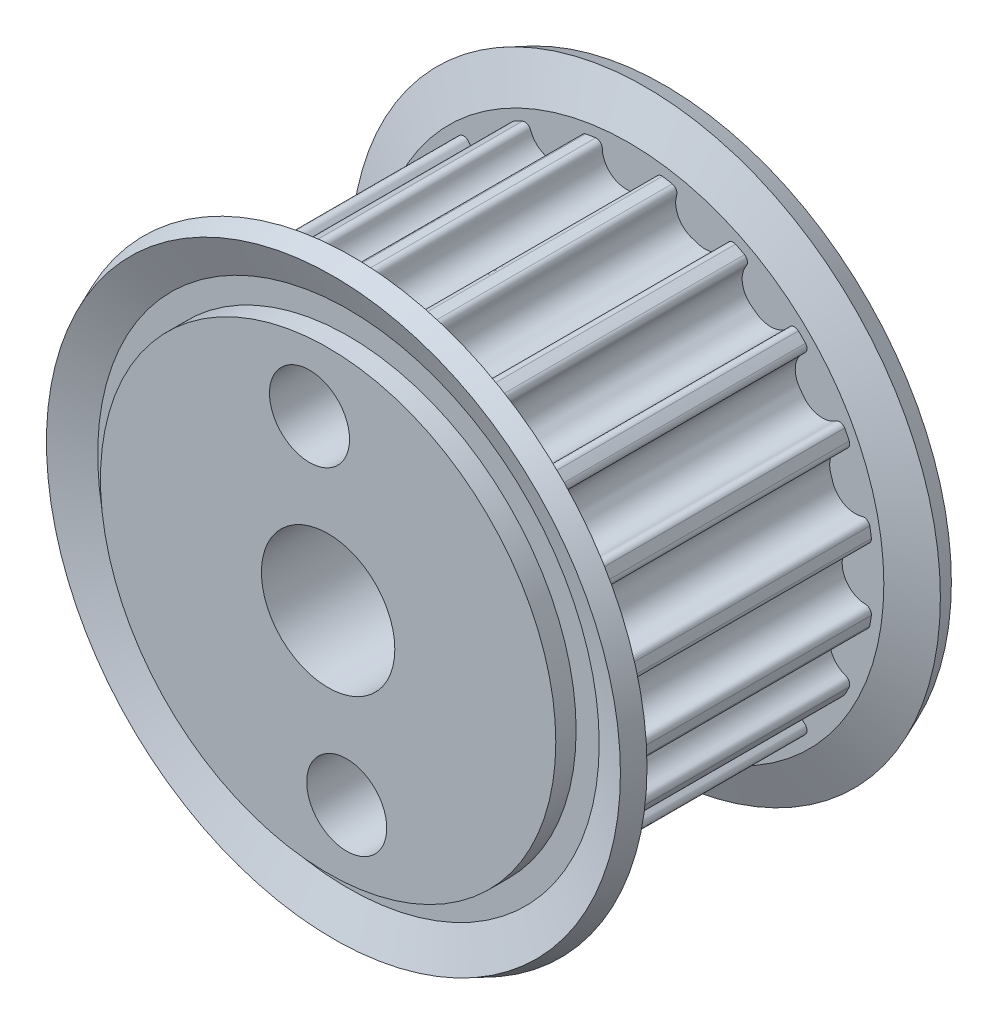
SolidWorks part; units mm, degrees
ref_plane "前视基准面" through (0, 0, 0) normal (0, 0, 1) x (1, 0, 0)
ref_plane "上视基准面" through (0, 0, 0) normal (0, 1, 0) x (1, 0, 0)
ref_plane "右视基准面" through (0, 0, 0) normal (1, 0, 0) x (0, 0, -1)
ref_axis "基准轴1" through (0, 0, 55) along (0, 0, -1)
sketch "SketchRevolveGearBelt01" plane through (0, 0, 0) normal (1, 0, 0) x (0, 0, -1)
  line L0 (0, 0) -> (1, 0) construction
  line L1 (6.4008, 0) -> (6.4008, 8.5326)
  line L2 (6.4008, 8.5326) -> (5.6388, 8.5326)
  line L3 (5.6388, 8.5326) -> (5.6388, 9.397)
  line L4 (5.6388, 9.397) -> (6.2015, 10.7556)
  line L5 (6.2015, 10.7556) -> (5.4975, 11.0472)
  line L6 (5.4975, 11.0472) -> (4.8768, 9.5486)
  line L7 (4.8768, 9.5486) -> (4.8768, 9.1676)
  line L8 (4.8768, 9.1676) -> (-4.8768, 9.1676)
  line L9 (-4.8768, 9.1676) -> (-4.8768, 9.5486)
  line L10 (-4.8768, 9.5486) -> (-5.4975, 11.0472)
  line L11 (-5.4975, 11.0472) -> (-6.2015, 10.7556)
  line L12 (-6.2015, 10.7556) -> (-5.6388, 9.397)
  line L13 (-5.6388, 9.397) -> (-5.6388, 8.5326)
  line L14 (-5.6388, 8.5326) -> (-6.4008, 8.5326)
  line L15 (-6.4008, 8.5326) -> (-6.4008, 0)
  line L16 (-6.4008, 0) -> (6.4008, 0)
  dimension "GearBeltFlange1OutsideLength" = 0.8644
  dimension "GearBeltFlange1X" = 0.5627
  dimension "GearBeltFlange1Y" = 1.3586
  dimension "GearBeltFlangeThickness" = 0.762
  dimension "GearBeltFlangeInside" = 0.381
  dimension "GearBeltOutsideDiameter" = 9.1676
  dimension "GearBeltFlange2X" = 0.5627
revolve "GearBelt01" add sketch "SketchRevolveGearBelt01" angle 360 about L0
sketch "SketchToothGearBelt01" plane through (0, 0, 0) normal (0, 0, 1) x (1, 0, 0)
  arc A0 (9.0809, 1.2614) -> (9.0809, -1.2614) centre (0, 0) cw
  spline S0 degree 3 poles (9.0809, -1.2614) (9.0827, -1.2485) (9.0837, -1.229) (9.0817, -1.203) (9.0786, -1.1837) (9.0738, -1.1647) (9.0675, -1.1462) (9.0596, -1.1283) (9.0502, -1.1112) (9.0393, -1.0949) (9.0272, -1.0796) (9.0137, -1.0654) (8.9991, -1.0524) (8.9835, -1.0407) (8.9669, -1.0303) (8.9495, -1.0215) (8.9314, -1.0141) (8.9127, -1.0083) (8.8936, -1.004) (8.8349, -0.9971) (8.7588, -0.996) (8.6681, -0.9767) (8.601, -0.9578) (8.5356, -0.9335) (8.4723, -0.9041) (8.4115, -0.8699) (8.3536, -0.8311) (8.2989, -0.7878) (8.2477, -0.7404) (8.2005, -0.6891) (8.1573, -0.6343) (8.1186, -0.5762) (8.0846, -0.5154) (8.0555, -0.452) (8.0314, -0.3865) (8.0124, -0.3194) (7.9989, -0.251) (7.9906, -0.1817) (7.9885, -0.1166) (7.989, -0.056) (7.9888, 0) (7.989, 0.056) (7.9885, 0.1166) (7.9906, 0.1817) (7.9989, 0.251) (8.0124, 0.3194) (8.0314, 0.3865) (8.0555, 0.452) (8.0846, 0.5154) (8.1186, 0.5762) (8.1573, 0.6343) (8.2005, 0.6891) (8.2477, 0.7404) (8.2989, 0.7878) (8.3536, 0.8311) (8.4115, 0.8699) (8.4723, 0.9041) (8.5356, 0.9335) (8.601, 0.9578) (8.6681, 0.9767) (8.7588, 0.996) (8.8349, 0.9971) (8.8936, 1.004) (8.9127, 1.0083) (8.9314, 1.0141) (8.9495, 1.0215) (8.9669, 1.0303) (8.9835, 1.0407) (8.9991, 1.0524) (9.0137, 1.0654) (9.0272, 1.0796) (9.0393, 1.0949) (9.0502, 1.1112) (9.0596, 1.1283) (9.0675, 1.1462) (9.0738, 1.1647) (9.0786, 1.1837) (9.0817, 1.203) (9.0837, 1.229) (9.0827, 1.2485) (9.0809, 1.2614) knots 0 0 0 0 0.010413 0.01562 0.020826 0.026033 0.031239 0.036446 0.041652 0.046859 0.052065 0.057272 0.062478 0.067685 0.072891 0.078098 0.083304 0.088511 0.093717 0.098924 0.135739 0.154317 0.172895 0.191472 0.21005 0.228628 0.247206 0.265784 0.284362 0.302939 0.321517 0.340095 0.358673 0.377251 0.395829 0.414406 0.432984 0.451562 0.47014 0.48507 0.5 0.51493 0.52986 0.548438 0.567016 0.585594 0.604171 0.622749 0.641327 0.659905 0.678483 0.697061 0.715638 0.734216 0.752794 0.771372 0.78995 0.808528 0.827105 0.845683 0.864261 0.901076 0.906283 0.911489 0.916696 0.921902 0.927109 0.932315 0.937522 0.942728 0.947935 0.953141 0.958348 0.963554 0.968761 0.973967 0.979174 0.98438 0.989587 1 1 1 1
extrude "ToothExtrudeCutGearBelt01" cut sketch "SketchToothGearBelt01" against normal blind 4.8768 and the other way blind 4.8768
pattern_circular "PatternGearBelt01" count 20 every 18 about axis through (0, 0, 55) along (0, 0, -1) of "ToothExtrudeCutGearBelt01"
sketch "BoreRevolveSketch" plane through (0, 0, 0) normal (1, 0, 0) x (0, 0, -1)
  line L0 (0, 0) -> (1, 0) construction
  line L1 (-6.4008, 0) -> (6.4008, 0)
  line L2 (6.4008, 0) -> (6.4008, 2.5)
  line L3 (6.4008, 2.5) -> (-6.4008, 2.5)
  line L4 (-6.4008, 2.5) -> (-6.4008, 0)
  dimension "TaperSide1" = 2.5
  dimension "TaperSide2" = 2.5
revolve "BoreRevolveCut" cut sketch "BoreRevolveSketch" angle 360 about L0
sketch "AuxiliarySketchGearBelt01" plane through (0, 0, 0) normal (0, 0, 1) x (1, 0, 0)
  circle A0 centre (0, 0) radius 9.5486 construction
  dimension "PitchDiameter" = 19.0972
sketch "草图1" plane through (0, 0, 6.4008) normal (0, 0, 1) x (1, 0, 0)
  line L0 (0.6974, -5.9593) -> (-0.6974, 5.9593) construction
  circle A0 centre (0.6974, -5.9593) radius 1.5
  circle A1 centre (-0.6974, 5.9593) radius 1.5
  dimension "D1" = 12
extrude "切除-拉伸1" cut sketch "草图1" against normal blind 13
